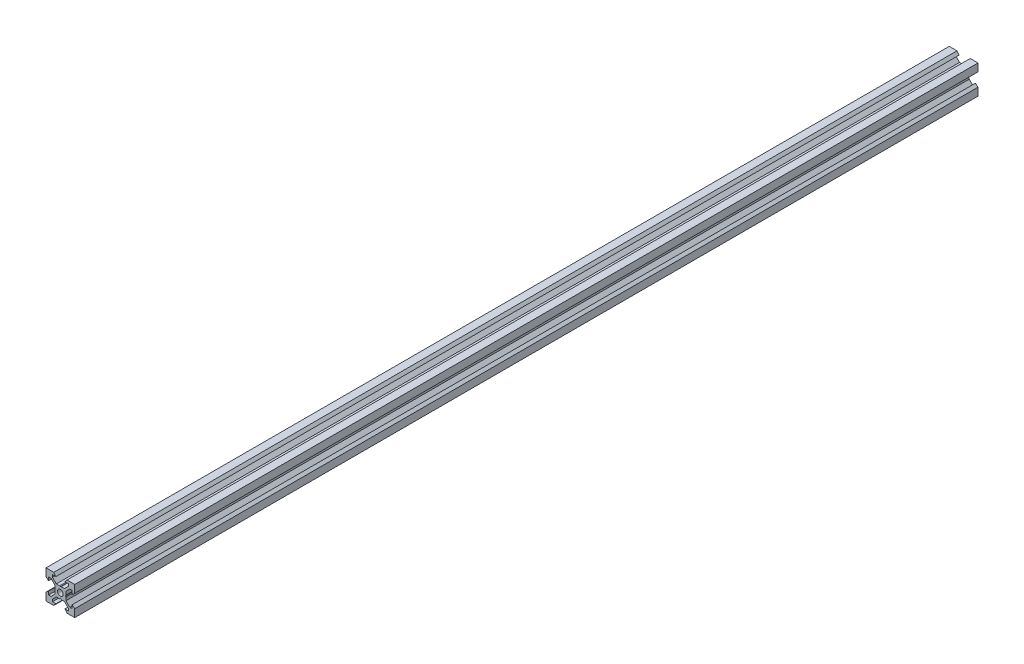
SolidWorks part; units mm, degrees
ref_plane "Front Plane" through (0, 0, 0) normal (0, 0, 1) x (1, 0, 0)
ref_plane "Top Plane" through (0, 0, 0) normal (0, 1, 0) x (1, 0, 0)
ref_plane "Right Plane" through (0, 0, 0) normal (1, 0, 0) x (0, 0, -1)
sketch "Sketch1" plane through (0, 0, 0) normal (0, 0, 1) x (1, 0, 0)
  line L0 (10, 10) -> (4.6104, 10) construction
  line L1 (10, 10) -> (10, 4.6104) construction
  line L2 (10, -10) -> (10, -4.6104) construction
  line L3 (10, -10) -> (4.6104, -10) construction
  line L4 (10, 10) -> (10, 4.6104)
  line L5 (6.5607, 5.5) -> (8.2, 5.5)
  line L6 (5.5, 8.2) -> (5.5, 6.5607)
  line L7 (10, 10) -> (4.6104, 10)
  line L8 (10, 10) -> (10, 4.6104)
  line L9 (6.5607, 5.5) -> (3.9, 2.8393)
  line L10 (5.5, 6.5607) -> (2.8393, 3.9)
  line L11 (10, 4.6104) -> (8.2, 3.1)
  line L12 (4.6104, 10) -> (3.1, 8.2)
  line L13 (8.2, 3.1) -> (8.2, 5.5)
  line L14 (3.1, 8.2) -> (5.5, 8.2)
  line L15 (-6.5607, 5.5) -> (-8.2, 5.5)
  line L16 (6.5607, -5.5) -> (8.2, -5.5)
  line L17 (3.1, -8.2) -> (5.5, -8.2)
  line L18 (8.2, -3.1) -> (8.2, -5.5)
  line L19 (4.6104, -10) -> (3.1, -8.2)
  line L20 (10, -4.6104) -> (8.2, -3.1)
  line L21 (0.5196, -3.9) -> (0, -3.6)
  line L22 (0.5196, 3.9) -> (0, 3.6)
  line L23 (3.6, 0) -> (3.9, -0.5196)
  line L24 (3.9, 0.5196) -> (3.6, 0)
  line L25 (3.9, 0.5196) -> (3.9, 2.8393)
  line L26 (2.8393, 3.9) -> (0.5196, 3.9)
  line L27 (3.9, -2.8393) -> (3.9, -0.5196)
  line L28 (2.8393, -3.9) -> (0.5196, -3.9)
  line L29 (5.5, -6.5607) -> (2.8393, -3.9)
  line L30 (6.5607, -5.5) -> (3.9, -2.8393)
  line L31 (10, -10) -> (10, -4.6104)
  line L32 (10, -10) -> (4.6104, -10)
  line L33 (5.5, -8.2) -> (5.5, -6.5607)
  line L34 (-6.5607, -5.5) -> (-8.2, -5.5)
  line L35 (10, -10) -> (10, -4.6104)
  line L36 (0, 0) -> (0, 8.2) construction
  line L37 (-10, -10) -> (-4.6104, -10) construction
  line L38 (-10, -10) -> (-10, -4.6104) construction
  line L39 (-10, 10) -> (-10, 4.6104) construction
  line L40 (-10, 10) -> (-4.6104, 10) construction
  line L41 (-10, -10) -> (-10, -4.6104)
  line L43 (-5.5, -8.2) -> (-5.5, -6.5607)
  line L44 (-10, -10) -> (-4.6104, -10)
  line L45 (-10, -10) -> (-10, -4.6104)
  line L46 (-6.5607, -5.5) -> (-3.9, -2.8393)
  line L47 (-5.5, -6.5607) -> (-2.8393, -3.9)
  line L48 (-2.8393, -3.9) -> (-0.5196, -3.9)
  line L49 (-3.9, -2.8393) -> (-3.9, -0.5196)
  line L50 (-2.8393, 3.9) -> (-0.5196, 3.9)
  line L51 (-3.9, 0.5196) -> (-3.9, 2.8393)
  line L52 (-3.9, 0.5196) -> (-3.6, 0)
  line L53 (-3.6, 0) -> (-3.9, -0.5196)
  line L54 (-0.5196, 3.9) -> (0, 3.6)
  line L55 (-0.5196, -3.9) -> (0, -3.6)
  line L56 (-10, -4.6104) -> (-8.2, -3.1)
  line L57 (-4.6104, -10) -> (-3.1, -8.2)
  line L58 (-8.2, -3.1) -> (-8.2, -5.5)
  line L59 (-3.1, -8.2) -> (-5.5, -8.2)
  line L60 (-10, -10) -> (10, -10) construction
  line L61 (-10, -10) -> (-10, 10) construction
  line L62 (-3.1, 8.2) -> (-5.5, 8.2)
  line L63 (-8.2, 3.1) -> (-8.2, 5.5)
  line L64 (-4.6104, 10) -> (-3.1, 8.2)
  line L65 (-10, 4.6104) -> (-8.2, 3.1)
  line L66 (-5.5, 6.5607) -> (-2.8393, 3.9)
  line L67 (-6.5607, 5.5) -> (-3.9, 2.8393)
  line L68 (-10, 10) -> (-10, 4.6104)
  line L69 (-10, 10) -> (-4.6104, 10)
  line L70 (-5.5, 8.2) -> (-5.5, 6.5607)
  line L71 (-10, 10) -> (10, 10) construction
  line L72 (-10, 10) -> (-10, 4.6104)
  line L73 (10, -10) -> (10, 10) construction
  line L74 (-10, -10) -> (10, 10) construction
  line L75 (-10, 10) -> (10, -10) construction
  circle A0 centre (0, 0) radius 2
  dimension "D7" = 4
  dimension "D1" = 20
  dimension "D2" = 5.3896
  dimension "D3" = 4.5
  dimension "D4" = 50
  dimension "D5" = 1.8
  dimension "D6" = 1.5104
  dimension "D8" = 5.5
  dimension "D9" = 120
  dimension "D10" = 0.3
  dimension "D11" = 2.3197
  dimension "D12" = 7.8
  dimension "D13" = 7.8
  dimension "D14" = 1.5
  dimension "D15" = 2.6607
extrude "Boss-Extrude1" add sketch "Sketch1" along normal mid plane 628.38 contours L70 L62 L64 L69 L68 L65 L63 L15 L67 L51 L52 L53 L49 L46 L34 L58 L56 L41 L44 L57 L59 L43 L47 L48 L55 L21 L28 L29 L33 L17 L19 L32 L31 L20 L18 L16 L30 L27 L23 L24 L25 L9 L5 L13 L11 L4 L7 L12 L14 L6 L10 region at (9.7172, 7.3052, 0)
